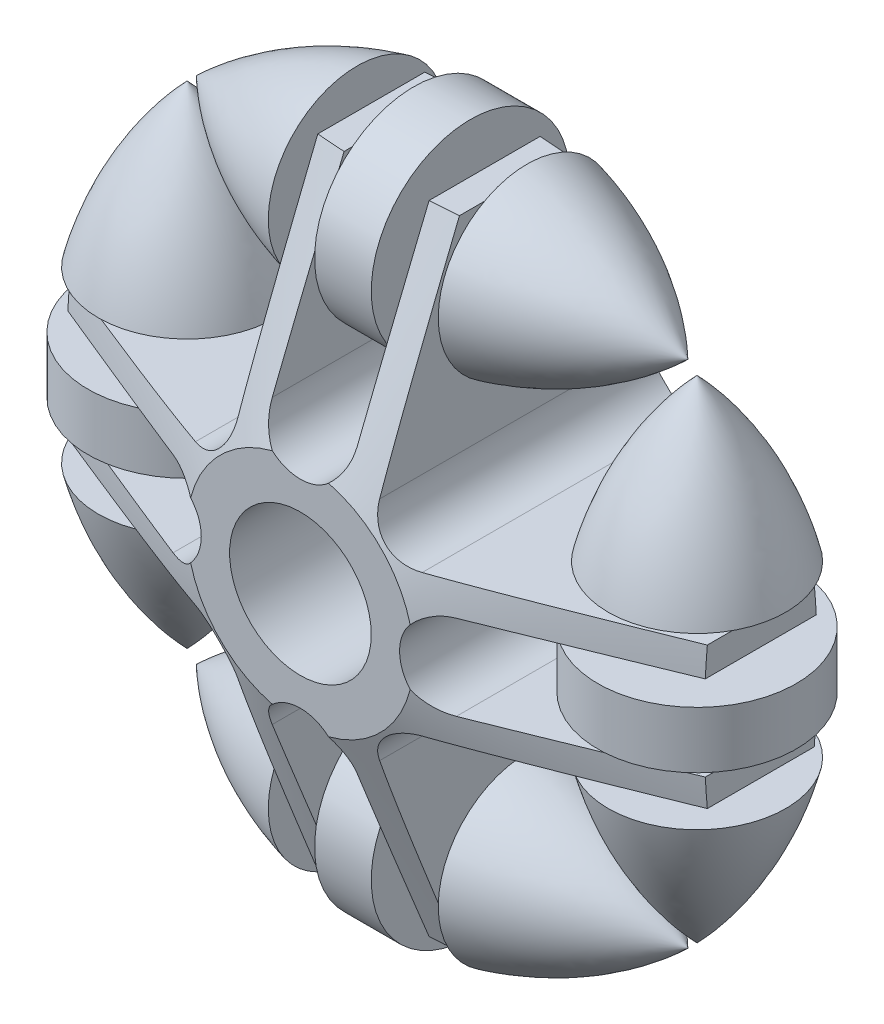
SolidWorks part; units mm, degrees
ref_plane "前视基准面" through (0, 0, 0) normal (0, 0, 1) x (1, 0, 0)
ref_plane "上视基准面" through (0, 0, 0) normal (0, 1, 0) x (1, 0, 0)
ref_plane "右视基准面" through (0, 0, 0) normal (1, 0, 0) x (0, 0, -1)
sketch "草图1" plane through (0, 0, 0) normal (0, 0, 1) x (1, 0, 0)
  line L0 (0, 0) -> (69.8665, 0) construction
  line L1 (0, 0) -> (0, 58.0263) construction
  line L2 (-5, 22.5) -> (-3, 22.5)
  line L3 (-5, 8) -> (-5, 22.5)
  line L4 (-3, 10) -> (-3, 22.5)
  line L5 (3, 22.5) -> (5, 22.5)
  line L6 (3, 10) -> (3, 22.5)
  line L7 (5, 8) -> (5, 22.5)
  line L8 (22.5, 5) -> (22.5, 3)
  line L9 (10, 3) -> (22.5, 3)
  line L10 (22.5, -3) -> (22.5, -5)
  line L11 (10, -3) -> (22.5, -3)
  line L12 (8, 5) -> (22.5, 5)
  line L13 (8, -5) -> (22.5, -5)
  line L14 (5, -22.5) -> (3, -22.5)
  line L15 (3, -10) -> (3, -22.5)
  line L16 (-3, -22.5) -> (-5, -22.5)
  line L17 (-3, -10) -> (-3, -22.5)
  line L18 (5, -8) -> (5, -22.5)
  line L19 (-5, -8) -> (-5, -22.5)
  line L20 (-22.5, -5) -> (-22.5, -3)
  line L21 (-10, -3) -> (-22.5, -3)
  line L22 (-22.5, 3) -> (-22.5, 5)
  line L23 (-10, 3) -> (-22.5, 3)
  line L24 (-8, -5) -> (-22.5, -5)
  line L25 (-8, 5) -> (-22.5, 5)
  circle A0 centre (0, 0) radius 5
  arc A1 (-3, 10) -> (3, 10) centre (0, 10) ccw
  arc A2 (10, 3) -> (10, -3) centre (10, 0) ccw
  arc A3 (3, -10) -> (-3, -10) centre (0, -10) ccw
  arc A4 (-10, -3) -> (-10, 3) centre (-10, 0) ccw
  arc A5 (-5, -8) -> (-8, -5) centre (-8, -8) ccw
  arc A6 (5, -8) -> (8, -5) centre (8, -8) cw
  arc A7 (8, 5) -> (5, 8) centre (8, 8) cw
  arc A8 (-8, 5) -> (-5, 8) centre (-8, 8) ccw
  point P11 (0, 7)
  point P12 (0, 5)
  point P24 (7, 0)
  point P34 (0, -7)
  point P44 (-7, 0)
  dimension "D1" = 10
  dimension "D2" = 6
  dimension "D6" = 3
  dimension "D3" = 22.5
  dimension "D4" = 2
  dimension "D5" = 4
extrude "凸台-拉伸1" add sketch "草图1" along normal mid plane 20
sketch "草图2" plane through (0, 0, 0) normal (1, 0, 0) x (0, 0, -1)
  line L0 (0, 0) -> (0, 26.2614) construction
  line L1 (-10, 8) -> (-10, 24.3673)
  line L2 (-10, 24.3673) -> (-3.2273, 24.3673)
  line L3 (-3.2273, 24.3673) -> (-10, 8)
  line L4 (-10, 22.5) -> (10, 22.5) construction
  line L5 (-10, 8) -> (10, 8) construction
  line L6 (-10, 8) -> (-10, 5) construction
  line L7 (3.2273, 24.3673) -> (10, 8)
  line L8 (10, 24.3673) -> (3.2273, 24.3673)
  line L9 (10, 8) -> (10, 24.3673)
  point P8 (-4, 22.5)
  point P18 (4, 22.5)
  dimension "D1" = 4
revolve "切除-旋转1" cut sketch "草图2" angle 360 about axis through (0, 0, 10) along (0, 0, -1)
sketch "草图3" plane through (0, 0, 0) normal (1, 0, 0) x (0, 0, -1)
  line L0 (0, 0) -> (0, 31.4796) construction
  circle A0 centre (0, 18) radius 7
  point P5 (0, 25)
  dimension "D1" = 14
  dimension "D2" = 25
extrude "凸台-拉伸2" add sketch "草图3" along normal mid plane 4 separate body
pattern_circular "阵列(圆周)1" count 4 over 360 about axis through (0, 0, 10) along (0, 0, -1) of bodies 103
sketch "草图4" plane through (0, 0, 0) normal (0, 0, 1) x (1, 0, 0)
  line L0 (2, 18) -> (27.6779, 18) construction
  line L1 (2, 11) -> (2, 25) construction
  line L2 (6, 24.2693) -> (6, 18)
  line L3 (6, 18) -> (17.3494, 18)
  arc A0 (17.3494, 18) -> (6, 24.2693) centre (0, 0) ccw
  dimension "D1" = 50
  dimension "D2" = 4
revolve "旋转1" add sketch "草图4" angle 360 about L0
pattern_circular "阵列(圆周)3" count 4 over 360 about axis through (0, 0, 10) along (0, 0, -1) of bodies 107
mirror "镜向1" about plane through (0, 0, 0) normal (1, 0, 0) of bodies 107
pattern_circular "阵列(圆周)4" count 4 over 360 about axis through (0, 0, 10) along (0, 0, -1) of bodies 111
